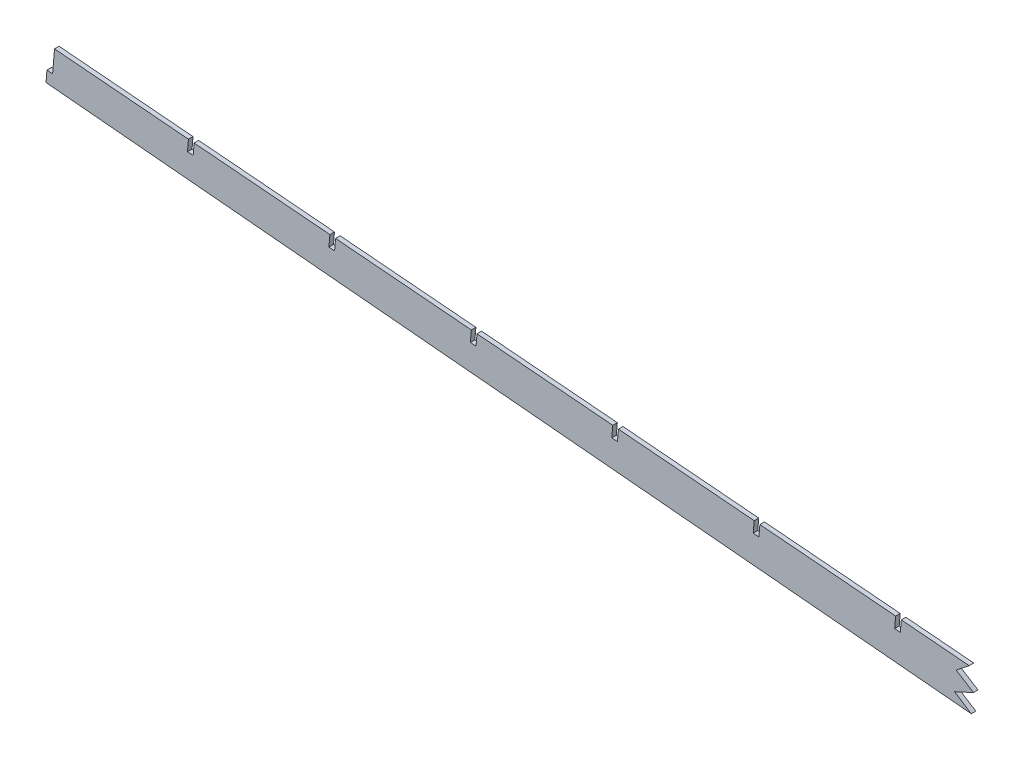
SolidWorks part; units mm, degrees
ref_plane "Front Plane" through (0, 0, 0) normal (0, 0, 1) x (1, 0, 0)
ref_plane "Top Plane" through (0, 0, 0) normal (0, 1, 0) x (1, 0, 0)
ref_plane "Right Plane" through (0, 0, 0) normal (1, 0, 0) x (0, 0, -1)
sketch "Sketch1" plane through (0, 0, 0) normal (0, 0, 1) x (1, 0, 0)
  line L0 (-949.6524, 80.0757) -> (-9.8872, -5.2596)
  line L1 (-945.9572, 86.1378) -> (-949.6524, 80.0757)
  line L8 (-6.7234, -5.5253) -> (-5.1293, 13.4579)
  line L9 (-5.1293, 13.4579) -> (-8.2932, 13.7235)
  line L10 (-8.2932, 13.7235) -> (-9.8872, -5.2596)
  line L11 (-9.8872, -5.2596) -> (-6.7234, -5.5253)
  line L12 (3.175, -5.8337) -> (3.175, 13.2163)
  line L13 (3.175, 13.2163) -> (0, 13.2163)
  line L14 (0, 13.2163) -> (0, -5.8337)
  line L15 (0, -5.8337) -> (3.175, -5.8337)
  line L17 (-943.1142, 119.9943) -> (-945.9572, 86.1378)
  line L18 (-945.9572, 86.1378) -> (-9.8872, -5.2596)
  line L19 (-6.7234, -5.5253) -> (0, -5.8337)
  line L20 (3.175, -5.8337) -> (152.4, -5.8337)
  line L21 (152.4, -5.8337) -> (152.4, 11.9463)
  line L22 (152.4, 11.9463) -> (69.85, 11.9463)
  line L23 (69.85, 11.9463) -> (25.4, 19.5663)
  line L24 (25.4, 19.5663) -> (-1.9861, 19.5663)
  line L25 (-1.9861, 19.5663) -> (-944.8986, 98.7448)
  line L26 (0, 13.2163) -> (0, 19.5663)
  line L27 (3.175, 13.2163) -> (3.175, 19.5663)
  line L28 (-5.1293, 13.4579) -> (-4.598, 19.7856)
  line L29 (-8.2932, 13.7235) -> (-7.7618, 20.0513)
  line L30 (-8.2932, 13.7235) -> (-945.4292, 92.426)
  line L31 (15.875, 19.5663) -> (15.875, 14.4863)
  line L32 (15.875, 14.4863) -> (19.05, 14.4863)
  line L33 (19.05, 14.4863) -> (19.05, 19.5663)
  line L34 (76.2, 6.8663) -> (76.2, 11.9463)
  line L35 (76.2, 6.8663) -> (79.375, 6.8663)
  line L36 (79.375, 6.8663) -> (79.375, 11.9463)
  line L37 (92.075, 11.9463) -> (92.075, 6.8663)
  line L38 (92.075, 6.8663) -> (95.25, 6.8663)
  line L39 (95.25, 6.8663) -> (95.25, 11.9463)
  line L40 (136.525, 11.9463) -> (136.525, 6.8663)
  line L41 (136.525, 6.8663) -> (139.7, 6.8663)
  line L42 (139.7, 6.8663) -> (139.7, 11.9463)
  line L44 (-949.6524, 80.0757) -> (-949.1211, 86.4035)
  line L45 (-949.1211, 86.4035) -> (-945.959, 86.1163)
  dimension "D1" = 25.4
  dimension "D2" = 6.35
extrude "Boss-Extrude1" add sketch "Sketch1" along normal blind 2.54 contours L42 L41 L40 L22 L39 L38 L37 L36 L35 L34 L23 L24 L33 L32 L31 L27 L12 L20 L21 | L30 L29 L25 L17 | L28 L8 L19 L14 L26 L24 L25 | L10 L11 L8 L9 | L14 L15 L12 L13 | L45 L44 L17 | L10 L30 L17 L18 | L18 L1 L0 region at (-635.1656, 53.6513, 0) region at (-948.2478, 84.1988, 0) region at (-398.9758, 39.6362, 0) region at (-7.5083, 4.0991, 0) region at (-476.4854, 56.2272, 0) region at (-2.8648, 6.1846, 0) region at (1.5875, 3.6913, 0) region at (71.853, 4.2703, 0)
sketch "Sketch2" plane through (0, 0, 2.54) normal (0, 0, 1) x (1, 0, 0)
  line L1 (-76.483, 72.8473) -> (-82.5095, 1.0799)
  line L3 (-155.6446, 77.1971) -> (-161.4339, 8.255)
  line L5 (-234.8005, 81.6162) -> (-240.3617, 15.3891)
  line L7 (-313.9625, 85.9617) -> (-319.2865, 22.5591)
  line L9 (-393.1191, 90.3714) -> (-398.2146, 29.6908)
  line L11 (-472.2837, 94.686) -> (-477.1388, 36.8682)
  line L13 (-551.4418, 99.0783) -> (-556.0668, 44.0001)
  line L15 (-630.6082, 103.3716) -> (-634.991, 51.1773)
  line L17 (-709.7674, 107.7507) -> (-713.9195, 58.3043)
  line L19 (-788.9364, 112.0121) -> (-792.8436, 65.483)
  line L21 (-868.0976, 116.3681) -> (-871.7723, 72.6069)
  line L23 (-73.3191, 72.5816) -> (-79.3456, 0.8143)
  line L25 (-152.4808, 76.9314) -> (-158.27, 7.9893)
  line L27 (-231.6366, 81.3506) -> (-237.1978, 15.1234)
  line L29 (-310.7986, 85.696) -> (-316.1227, 22.2934)
  line L31 (-389.9552, 90.1057) -> (-395.0507, 29.4251)
  line L33 (-469.1198, 94.4203) -> (-473.9749, 36.6025)
  line L35 (-548.2779, 98.8126) -> (-552.903, 43.7344)
  line L37 (-627.4443, 103.1059) -> (-631.8272, 50.9116)
  line L39 (-706.6035, 107.485) -> (-710.7556, 58.0386)
  line L41 (-785.7726, 111.7464) -> (-789.6797, 65.2173)
  line L43 (-864.9337, 116.1024) -> (-868.6084, 72.3413)
  line L45 (-8.2932, 13.7235) -> (-945.4292, 92.426)
  line L47 (-7.7618, 20.0513) -> (-944.8986, 98.7448)
  line M27 (-7.7618, 20.0513) -> (-944.8986, 98.7448)
extrude "Cut-Extrude1" cut sketch "Sketch2" against normal through all and the other way through all contours L45 L43 L21 M27 | L45 L41 L19 M27 | L45 L39 L17 M27 | L45 L37 L15 M27 | L45 L35 L13 M27 | L45 L33 L11 M27 | L45 L31 L9 M27 | L45 L29 L7 M27 | L45 L27 L5 M27 | L45 L25 L3 M27 | L45 L23 L1 M27 region at (-79.0879, 22.8549, 2.54) region at (-158.0579, 29.4865, 2.54) region at (-237.0279, 36.1182, 2.54) region at (-315.998, 42.7499, 2.54) region at (-394.968, 49.3816, 2.54) region at (-473.938, 56.0132, 2.54) region at (-552.9081, 62.6449, 2.54) region at (-631.8781, 69.2766, 2.54) region at (-710.8481, 75.9083, 2.54) region at (-789.8182, 82.54, 2.54) region at (-868.7882, 89.1716, 2.54)
sketch "Sketch3" plane through (0, 0, 2.54) normal (0, 0, 1) x (1, 0, 0)
  line L0 (-434.1875, 55.8592) -> (-441.4445, 50.0741)
  line L1 (-396.2844, 52.6764) -> (-472.0906, 59.042) construction
  line L2 (-441.4445, 50.0741) -> (-431.803, 44.0226)
  line L3 (-431.803, 44.0226) -> (-442.3497, 39.1715)
  line L4 (-442.3497, 39.1715) -> (-433.0143, 33.1624)
  line L5 (-949.6524, 80.0757) -> (-9.8872, -5.2596) construction
  line L6 (-434.1875, 55.8592) -> (201.2475, 33.1624)
  line L7 (201.2475, 33.1624) -> (148.3266, -67.6483)
  line L8 (148.3266, -67.6483) -> (-433.0143, 33.1624)
extrude "Cut-Extrude2" cut sketch "Sketch3" against normal blind 7.62 contours L8 L4 L3 L2 L0 L6 L7
